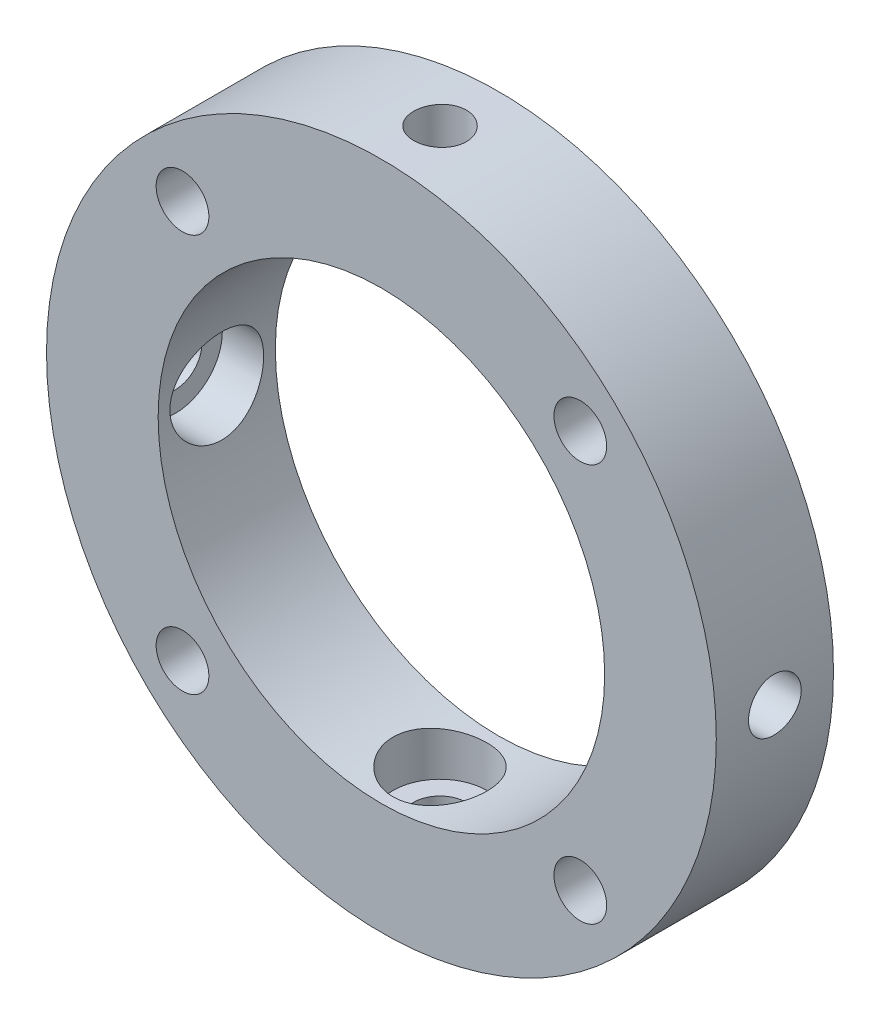
SolidWorks part; units mm, degrees
ref_plane "Front Plane" through (0, 0, 0) normal (0, 0, 1) x (1, 0, 0)
ref_plane "Top Plane" through (0, 0, 0) normal (0, 1, 0) x (1, 0, 0)
ref_plane "Right Plane" through (0, 0, 0) normal (1, 0, 0) x (0, 0, -1)
sketch "Sketch1" plane through (0, 0, 0) normal (0, 0, 1) x (1, 0, 0)
  circle A0 centre (0, 0) radius 28.575
  dimension "D1" = 57.15
extrude "Boss-Extrude1" add sketch "Sketch1" along normal blind 10
sketch "Sketch2" plane through (0, 0, 10) normal (0, 0, 1) x (1, 0, 0)
  circle A0 centre (0, 0) radius 19.05
  dimension "D1" = 38.1
extrude "Cut-Extrude1" cut sketch "Sketch2" against normal through all
ref_plane "Plane1" through (0, 28.575, 0) normal (0, 1, 0) x (1, 0, 0)
sketch "Sketch5" plane through (0, 28.575, 0) normal (0, 1, 0) x (1, 0, 0)
  circle A0 centre (0, -5) radius 2.25
  dimension "D2" = 4.5
  dimension "D1" = 5
extrude "Cut-Extrude2" cut sketch "Sketch5" against normal through all
sketch "Sketch6" plane through (0, 0, 10) normal (0, 0, 1) x (1, 0, 0)
  line L0 (0, 28.575) -> (0, -28.575) construction
  line L1 (5.5, 28.575) -> (-5.5, 28.575) construction
  line L2 (0, 0) -> (-16.9706, 16.9706) construction
  circle A1 centre (0, 0) radius 28.575 construction
  circle A3 centre (0, 0) radius 24 construction
  circle A4 centre (-16.9706, 16.9706) radius 2.25
  circle A5 centre (16.9706, 16.9706) radius 2.25
  circle A6 centre (16.9706, -16.9706) radius 2.25
  circle A7 centre (-16.9706, -16.9706) radius 2.25
  point P21 (0, 0)
  dimension "D2" = 45
  dimension "D1" = 48
  dimension "D3" = 4.5
  dimension "D4" = 4
extrude "Cut-Extrude3" cut sketch "Sketch6" against normal through all
ref_plane "Offset to Inner Ring" through (0, 18.575, 0) normal (0, 1, 0) x (1, 0, 0)
sketch "Sketch7" plane through (0, 28.575, 0) normal (0, 1, 0) x (1, 0, 0)
  circle A0 centre (0, -5) radius 4
  circle A3 centre (0, -5) radius 2.25
  circle A5 centre (0, -5) radius 2.25 construction
  dimension "D1" = 8
ref_plane "Other Side Plane" through (0, -18.575, 0) normal (0, 1, 0) x (1, 0, 0)
extrude "Cut-Extrude5" cut sketch "Sketch7" along normal blind 4 from surface starting at plane "Offset to Inner Ring"
extrude "Cut-Extrude6" cut sketch "Sketch7<4>" against normal blind 4 from surface starting at plane "Other Side Plane"
sketch "Sketch7<4>" plane through (0, 28.575, 0) normal (0, 1, 0) x (1, 0, 0) same geometry as "Sketch7"
pattern_circular "CirPattern6" count 2 every 90 about axis through (0, 0, 10) along (0, 0, 1) of "Cut-Extrude5", "Cut-Extrude6", "Cut-Extrude2"
